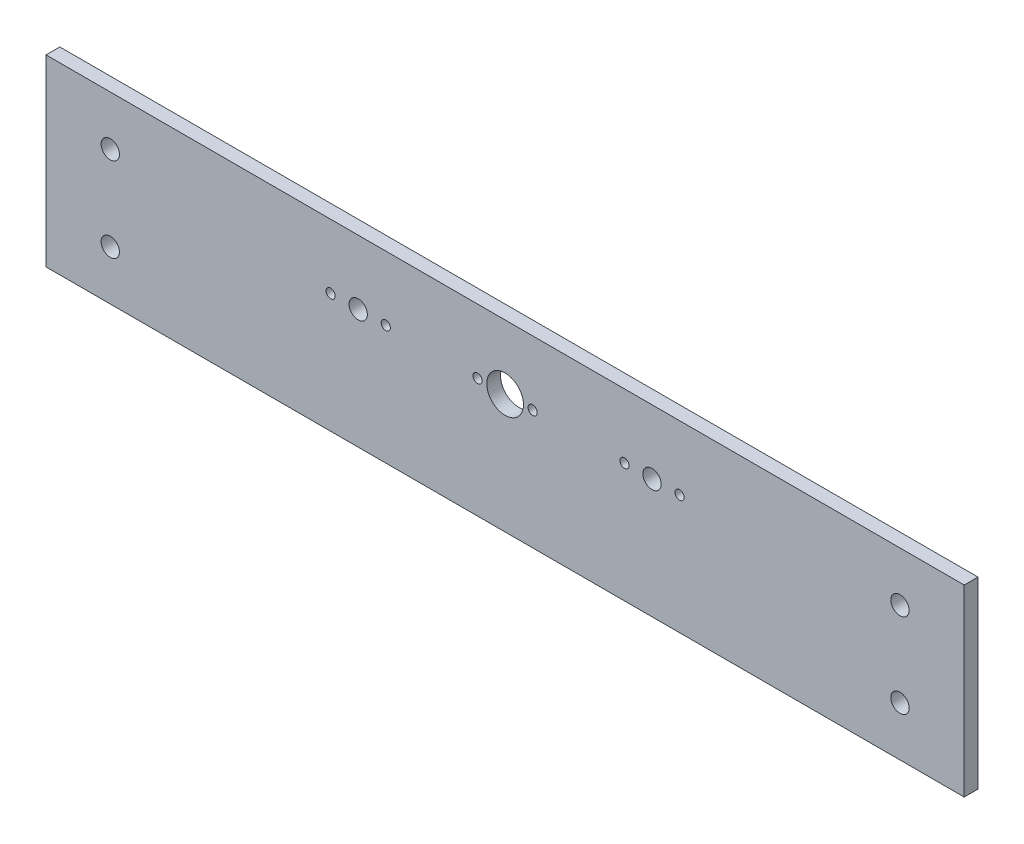
SolidWorks part; units mm, degrees
ref_plane "Front Plane" through (0, 0, 0) normal (0, 0, 1) x (1, 0, 0)
ref_plane "Top Plane" through (0, 0, 0) normal (0, 1, 0) x (1, 0, 0)
ref_plane "Right Plane" through (0, 0, 0) normal (1, 0, 0) x (0, 0, -1)
sketch "Sketch2" plane through (0, 0, 0) normal (0, 0, 1) x (1, 0, 0)
  line L1 (0, 100) -> (500, 100)
  line L2 (0, 100) -> (0, 0)
  line L3 (0, 0) -> (500, 0)
  line L4 (500, 100) -> (500, 0)
  dimension "D1" = 100
  dimension "D2" = 500
extrude "Boss-Extrude1" add sketch "Sketch2" along normal blind 7.5
sketch "Sketch9" plane through (0, 0, 7.5) normal (0, 0, 1) x (1, 0, 0)
  circle A0 centre (170, 65) radius 5
  circle A1 centre (185, 65) radius 2.5
  circle A2 centre (155, 65) radius 2.5
  circle A3 centre (330, 65) radius 5
  circle A4 centre (345, 65) radius 2.5
  circle A5 centre (315, 65) radius 2.5
  circle A6 centre (250, 65) radius 10
  circle A7 centre (265, 65) radius 2.5
  circle A8 centre (235, 65) radius 2.5
extrude "Cut-Extrude3" cut sketch "Sketch9" against normal through all
sketch "Sketch11" plane through (0, 0, 7.5) normal (0, 0, 1) x (1, 0, 0)
  circle A0 centre (35, 73) radius 5
  circle A1 centre (35, 27) radius 5
  circle A2 centre (465, 27) radius 5
  circle A3 centre (465, 73) radius 5
  dimension "D2" = 46
extrude "Cut-Extrude4" cut sketch "Sketch11" against normal through all
